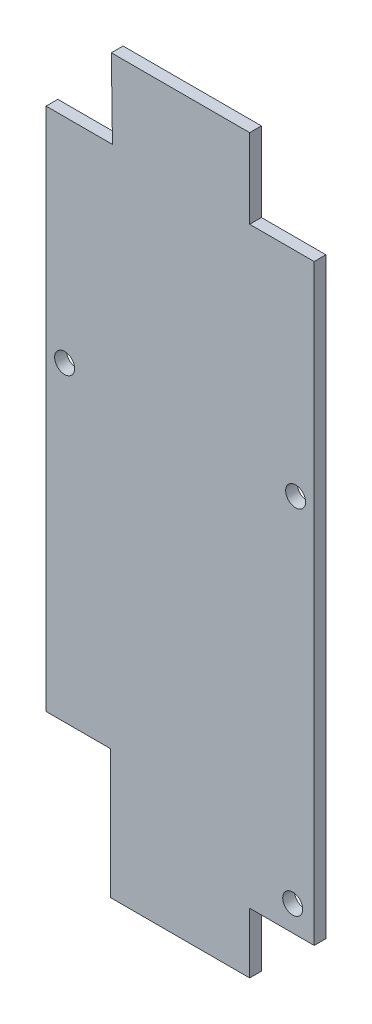
SolidWorks part; units mm, degrees
ref_plane "Front Plane" through (0, 0, 0) normal (0, 0, 1) x (1, 0, 0)
ref_plane "Top Plane" through (0, 0, 0) normal (0, 1, 0) x (1, 0, 0)
ref_plane "Right Plane" through (0, 0, 0) normal (1, 0, 0) x (0, 0, -1)
sketch "Sketch1" plane through (0, 0, 0) normal (0, 0, 1) x (1, 0, 0)
  line L61 (-30.8483, -49.6887) -> (-30.8483, -98.317)
  line L62 (-30.8483, -98.317) -> (-22.1171, -98.317)
  line L63 (-22.1171, -98.317) -> (-22.1171, -115.7795)
  line L64 (-22.1171, -115.7795) -> (-3.283, -115.7795)
  line L65 (-3.283, -115.7795) -> (-3.283, -98.317)
  line L66 (-3.283, -98.317) -> (5.4483, -98.317)
  line L67 (5.4483, -98.317) -> (5.4483, -49.6887)
  line L71 (5.4483, -49.6887) -> (5.4483, -27.4129)
  line L72 (5.4483, -27.4129) -> (-3.283, -27.4129)
  line L73 (-3.283, -27.4129) -> (-3.283, -16.6687)
  line L74 (-3.283, -16.6687) -> (-22.0149, -16.6687)
  line L75 (-22.0149, -16.6687) -> (-21.8622, -27.3367)
  line L76 (-21.8622, -27.3367) -> (-30.8483, -27.3367)
  line L77 (-30.8483, -27.3367) -> (-30.8483, -49.6887)
extrude "Boss-Extrude1" add sketch "Sketch1" along normal blind 1.5875
sketch "Sketch2" plane through (0, 0, 1.5875) normal (0, 0, 1) x (1, 0, 0)
  line L0 (5.4483, -98.317) -> (5.4483, -27.4129) construction
  line L1 (-3.283, -98.317) -> (5.4483, -98.317)
  line L2 (-3.283, -98.317) -> (-3.283, -107.6007)
  line L3 (-3.283, -107.6007) -> (5.4483, -107.6007)
  line L4 (5.4483, -98.317) -> (5.4483, -107.6007)
  line L5 (-3.283, -98.317) -> (5.4483, -107.6007) construction
  line L6 (-3.283, -107.6007) -> (5.4483, -98.317) construction
  line L7 (-3.283, -98.317) -> (5.4483, -98.317) construction
  point P4 (1.0827, -102.9589)
extrude "Boss-Extrude2" add sketch "Sketch2" against normal through all
hole_wizard "#2 Clearance Hole1" positions "Sketch4" profile "Sketch3" hole size "#2" standard "ANSI Inch" end condition through all
sketch "Sketch4" plane through (0, 0, 1.5875) normal (0, 0, 1) x (1, 0, 0)
  point P0 (2.54, -104.14)
  point P2 (-28.3369, -56.1975)
  point P4 (2.9369, -56.1975)
sketch "Sketch3" plane through (2.54, -104.14, 1.5875) normal (1, 0, 0) x (0, -1, 0)
  line L0 (0, 0) -> (0, 1.5875)
  line L1 (0, 1.5875) -> (1.3525, 1.5875)
  line L2 (1.3525, 1.5875) -> (1.3525, 0)
  line L5 (1.3525, 0) -> (0, 0)
  line L11 (0, -6.35) -> (0, 107.95) construction
  dimension "Thru Hole Dia." = 2.7051
  dimension "Thru Hole Depth" = 1.5875
sketch "Sketch5" plane through (0, 0, 0) normal (0, 0, -1) x (-1, 0, 0)
  line L6 (6.7628, -52.8637) -> (6.7628, -57.3087)
  line L7 (18.2563, -52.4827) -> (7.1438, -52.4827)
  line L8 (18.6373, -57.3087) -> (18.6373, -52.8637)
  line L9 (7.1438, -57.6897) -> (18.2563, -57.6897)
  line L10 (6.7628, -52.8637) -> (6.7628, -57.3087)
  line L11 (18.2563, -52.4827) -> (7.1438, -52.4827)
  line L12 (18.6373, -57.3087) -> (18.6373, -52.8637)
  line L13 (7.1438, -57.6897) -> (18.2563, -57.6897)
  line L14 (-1.9685, -42.0687) -> (-1.9685, -46.5137)
  line L15 (9.525, -41.6877) -> (-1.5875, -41.6877)
  line L16 (9.906, -46.5137) -> (9.906, -42.0687)
  line L17 (-1.5875, -46.8947) -> (9.525, -46.8947)
  line L18 (-1.9685, -42.0687) -> (-1.9685, -46.5137)
  line L19 (9.525, -41.6877) -> (-1.5875, -41.6877)
  line L20 (9.906, -46.5137) -> (9.906, -42.0687)
  line L21 (-1.5875, -46.8947) -> (9.525, -46.8947)
  line L22 (15.494, -42.0687) -> (15.494, -46.5137)
  line L23 (26.9875, -41.6877) -> (15.875, -41.6877)
  line L24 (27.3685, -46.5137) -> (27.3685, -42.0687)
  line L25 (15.875, -46.8947) -> (26.9875, -46.8947)
  line L26 (15.494, -42.0687) -> (15.494, -46.5137)
  line L27 (26.9875, -41.6877) -> (15.875, -41.6877)
  line L28 (27.3685, -46.5137) -> (27.3685, -42.0687)
  line L29 (15.875, -46.8947) -> (26.9875, -46.8947)
  line L30 (15.494, -31.2737) -> (15.494, -35.7187)
  line L31 (26.9875, -30.8927) -> (15.875, -30.8927)
  line L32 (27.3685, -35.7187) -> (27.3685, -31.2737)
  line L33 (15.875, -36.0997) -> (26.9875, -36.0997)
  line L34 (15.494, -31.2737) -> (15.494, -35.7187)
  line L35 (26.9875, -30.8927) -> (15.875, -30.8927)
  line L36 (27.3685, -35.7187) -> (27.3685, -31.2737)
  line L37 (15.875, -36.0997) -> (26.9875, -36.0997)
  line L38 (-1.9685, -31.2737) -> (-1.9685, -35.7187)
  line L39 (9.525, -30.8927) -> (-1.5875, -30.8927)
  line L40 (9.906, -35.7187) -> (9.906, -31.2737)
  line L41 (-1.5875, -36.0997) -> (9.525, -36.0997)
  line L42 (-1.9685, -31.2737) -> (-1.9685, -35.7187)
  line L43 (9.525, -30.8927) -> (-1.5875, -30.8927)
  line L44 (9.906, -35.7187) -> (9.906, -31.2737)
  line L45 (-1.5875, -36.0997) -> (9.525, -36.0997)
  line L46 (6.7628, -20.4787) -> (6.7628, -24.9237)
  line L47 (18.2563, -20.0977) -> (7.1438, -20.0977)
  line L48 (18.6373, -24.9237) -> (18.6373, -20.4787)
  line L49 (7.1438, -25.3047) -> (18.2563, -25.3047)
  line L50 (6.7628, -20.4787) -> (6.7628, -24.9237)
  line L51 (18.2563, -20.0977) -> (7.1438, -20.0977)
  line L52 (18.6373, -24.9237) -> (18.6373, -20.4787)
  line L53 (7.1438, -25.3047) -> (18.2563, -25.3047)
  line L54 (9.7473, -71.6915) -> (-1.8097, -71.6915)
  line L55 (9.7473, -77.216) -> (9.7473, -71.6915)
  line L56 (-1.8097, -77.216) -> (9.7473, -77.216)
  line L57 (-1.8097, -71.6915) -> (-1.8097, -77.216)
  line L58 (9.7473, -71.6915) -> (-1.8097, -71.6915)
  line L59 (9.7473, -77.216) -> (9.7473, -71.6915)
  line L60 (-1.8097, -77.216) -> (9.7473, -77.216)
  line L61 (-1.8097, -71.6915) -> (-1.8097, -77.216)
  line L63 (9.7473, -71.1835) -> (9.7473, -65.659)
  line L64 (-1.8097, -71.1835) -> (9.7473, -71.1835)
  line L65 (-1.8097, -65.659) -> (-1.8097, -71.1835)
  line L66 (9.7473, -65.659) -> (-1.8097, -65.659)
  line L67 (9.7473, -71.1835) -> (9.7473, -65.659)
  line L68 (-1.8097, -71.1835) -> (9.7473, -71.1835)
  line L69 (-1.8097, -65.659) -> (-1.8097, -71.1835)
  line L70 (9.7473, -65.659) -> (-1.8097, -65.659)
  line L71 (12.7, -106.6165) -> (12.7, -106.1085) construction
  line L72 (27.2098, -71.1835) -> (27.2098, -65.659)
  line L73 (15.6528, -71.1835) -> (27.2098, -71.1835)
  line L74 (15.6528, -65.659) -> (15.6528, -71.1835)
  line L75 (27.2098, -65.659) -> (15.6528, -65.659)
  line L76 (27.2098, -71.1835) -> (27.2098, -65.659)
  line L77 (15.6528, -71.1835) -> (27.2098, -71.1835)
  line L78 (15.6528, -65.659) -> (15.6528, -71.1835)
  line L79 (27.2098, -65.659) -> (15.6528, -65.659)
  line L80 (27.2098, -71.6915) -> (15.6528, -71.6915)
  line L81 (27.2098, -77.216) -> (27.2098, -71.6915)
  line L82 (15.6528, -77.216) -> (27.2098, -77.216)
  line L83 (15.6528, -71.6915) -> (15.6528, -77.216)
  line L84 (27.2098, -71.6915) -> (15.6528, -71.6915)
  line L85 (27.2098, -77.216) -> (27.2098, -71.6915)
  line L86 (15.6528, -77.216) -> (27.2098, -77.216)
  line L87 (15.6528, -71.6915) -> (15.6528, -77.216)
  line L88 (21.4313, -89.154) -> (21.4313, -88.646) construction
  line L89 (27.2098, -88.646) -> (27.2098, -83.1215)
  line L90 (15.6528, -88.646) -> (27.2098, -88.646)
  line L91 (15.6528, -83.1215) -> (15.6528, -88.646)
  line L92 (27.2098, -83.1215) -> (15.6528, -83.1215)
  line L93 (27.2098, -88.646) -> (27.2098, -83.1215)
  line L94 (15.6528, -88.646) -> (27.2098, -88.646)
  line L95 (15.6528, -83.1215) -> (15.6528, -88.646)
  line L96 (27.2098, -83.1215) -> (15.6528, -83.1215)
  line L97 (3.9688, -89.154) -> (3.9688, -88.646) construction
  line L98 (9.7473, -88.646) -> (9.7473, -83.1215)
  line L99 (-1.8097, -88.646) -> (9.7473, -88.646)
  line L100 (-1.8097, -83.1215) -> (-1.8097, -88.646)
  line L101 (9.7473, -83.1215) -> (-1.8097, -83.1215)
  line L102 (9.7473, -88.646) -> (9.7473, -83.1215)
  line L103 (-1.8097, -88.646) -> (9.7473, -88.646)
  line L104 (-1.8097, -83.1215) -> (-1.8097, -88.646)
  line L105 (9.7473, -83.1215) -> (-1.8097, -83.1215)
  line L106 (27.2098, -89.154) -> (15.6528, -89.154)
  line L107 (27.2098, -94.6785) -> (27.2098, -89.154)
  line L108 (15.6528, -94.6785) -> (27.2098, -94.6785)
  line L109 (15.6528, -89.154) -> (15.6528, -94.6785)
  line L110 (27.2098, -89.154) -> (15.6528, -89.154)
  line L111 (27.2098, -94.6785) -> (27.2098, -89.154)
  line L112 (15.6528, -94.6785) -> (27.2098, -94.6785)
  line L113 (15.6528, -89.154) -> (15.6528, -94.6785)
  line L114 (9.7473, -89.154) -> (-1.8097, -89.154)
  line L115 (9.7473, -94.6785) -> (9.7473, -89.154)
  line L116 (-1.8097, -94.6785) -> (9.7473, -94.6785)
  line L117 (-1.8097, -89.154) -> (-1.8097, -94.6785)
  line L118 (9.7473, -89.154) -> (-1.8097, -89.154)
  line L119 (9.7473, -94.6785) -> (9.7473, -89.154)
  line L120 (-1.8097, -94.6785) -> (9.7473, -94.6785)
  line L121 (-1.8097, -89.154) -> (-1.8097, -94.6785)
  line L122 (3.9688, -71.6915) -> (3.9688, -71.1835) construction
  line L123 (18.4785, -106.1085) -> (18.4785, -100.584)
  line L124 (6.9215, -106.1085) -> (18.4785, -106.1085)
  line L125 (6.9215, -100.584) -> (6.9215, -106.1085)
  line L126 (18.4785, -100.584) -> (6.9215, -100.584)
  line L127 (18.4785, -106.1085) -> (18.4785, -100.584)
  line L128 (6.9215, -106.1085) -> (18.4785, -106.1085)
  line L129 (6.9215, -100.584) -> (6.9215, -106.1085)
  line L130 (18.4785, -100.584) -> (6.9215, -100.584)
  line L131 (18.4785, -106.6165) -> (6.9215, -106.6165)
  line L132 (18.4785, -112.141) -> (18.4785, -106.6165)
  line L133 (6.9215, -112.141) -> (18.4785, -112.141)
  line L134 (6.9215, -106.6165) -> (6.9215, -112.141)
  line L135 (18.4785, -106.6165) -> (6.9215, -106.6165)
  line L136 (18.4785, -112.141) -> (18.4785, -106.6165)
  line L137 (6.9215, -112.141) -> (18.4785, -112.141)
  line L138 (6.9215, -106.6165) -> (6.9215, -112.141)
  line L139 (21.4313, -71.1835) -> (21.4313, -71.6915) construction
  line L147 (-5.4483, -107.6007) -> (3.283, -107.6007)
  line L148 (3.283, -107.6007) -> (3.283, -115.7795)
  line L149 (3.283, -115.7795) -> (22.1171, -115.7795)
  line L150 (22.1171, -115.7795) -> (22.1171, -98.317)
  line L151 (22.1171, -98.317) -> (30.8483, -98.317)
  line L152 (30.8483, -98.317) -> (30.8483, -27.3367)
  line L153 (30.8483, -27.3367) -> (21.8622, -27.3367)
  line L154 (21.8622, -27.3367) -> (22.0149, -16.6687)
  line L155 (22.0149, -16.6687) -> (3.283, -16.6687)
  line L156 (3.283, -16.6687) -> (3.283, -27.4129)
  line L157 (3.283, -27.4129) -> (-5.4483, -27.4129)
  line L158 (-5.4483, -27.4129) -> (-5.4483, -107.6007)
  line L159 (-5.4483, -107.6007) -> (3.283, -107.6007)
  line L160 (3.283, -107.6007) -> (3.283, -115.7795)
  line L161 (3.283, -115.7795) -> (22.1171, -115.7795)
  line L162 (22.1171, -115.7795) -> (22.1171, -98.317)
  line L163 (22.1171, -98.317) -> (30.8483, -98.317)
  line L164 (30.8483, -98.317) -> (30.8483, -27.3367)
  line L165 (30.8483, -27.3367) -> (21.8622, -27.3367)
  line L166 (21.8622, -27.3367) -> (22.0149, -16.6687)
  line L167 (22.0149, -16.6687) -> (3.283, -16.6687)
  line L168 (3.283, -16.6687) -> (3.283, -27.4129)
  line L169 (3.283, -27.4129) -> (-5.4483, -27.4129)
  line L170 (-5.4483, -27.4129) -> (-5.4483, -107.6007)
  circle A0 centre (12.7, -106.3625) radius 2.8509
  circle A1 centre (-2.9369, -56.1975) radius 1.3526
  circle A2 centre (-2.9369, -56.1975) radius 1.3525
  circle A3 centre (28.3369, -56.1975) radius 1.3526
  circle A4 centre (28.3369, -56.1975) radius 1.3526
  circle A5 centre (-2.54, -104.14) radius 1.3526
  circle A6 centre (-2.54, -104.14) radius 1.3525
  circle A7 centre (3.9688, -88.9) radius 2.8509
  circle A8 centre (21.4313, -88.9) radius 2.8509
  circle A9 centre (21.4313, -71.4375) radius 2.8509
  arc A10 (7.1438, -52.4827) -> (6.7628, -52.8637) centre (7.1438, -52.8637) ccw
  arc A11 (18.6373, -52.8637) -> (18.2563, -52.4827) centre (18.2563, -52.8637) ccw
  arc A12 (18.2563, -57.6897) -> (18.6373, -57.3087) centre (18.2563, -57.3087) ccw
  arc A13 (6.7628, -57.3087) -> (7.1438, -57.6897) centre (7.1438, -57.3087) ccw
  arc A14 (7.1438, -52.4827) -> (6.7628, -52.8637) centre (7.1438, -52.8637) ccw
  arc A15 (18.6373, -52.8637) -> (18.2563, -52.4827) centre (18.2563, -52.8637) ccw
  arc A16 (18.2563, -57.6897) -> (18.6373, -57.3087) centre (18.2563, -57.3087) ccw
  arc A17 (6.7628, -57.3087) -> (7.1438, -57.6897) centre (7.1438, -57.3087) ccw
  arc A18 (-1.5875, -41.6877) -> (-1.9685, -42.0687) centre (-1.5875, -42.0687) ccw
  arc A19 (9.906, -42.0687) -> (9.525, -41.6877) centre (9.525, -42.0687) ccw
  arc A20 (9.525, -46.8947) -> (9.906, -46.5137) centre (9.525, -46.5137) ccw
  arc A21 (-1.9685, -46.5137) -> (-1.5875, -46.8947) centre (-1.5875, -46.5137) ccw
  arc A22 (-1.5875, -41.6877) -> (-1.9685, -42.0687) centre (-1.5875, -42.0687) ccw
  arc A23 (9.906, -42.0687) -> (9.525, -41.6877) centre (9.525, -42.0687) ccw
  arc A24 (9.525, -46.8947) -> (9.906, -46.5137) centre (9.525, -46.5137) ccw
  arc A25 (-1.9685, -46.5137) -> (-1.5875, -46.8947) centre (-1.5875, -46.5137) ccw
  arc A26 (15.875, -41.6877) -> (15.494, -42.0687) centre (15.875, -42.0687) ccw
  arc A27 (27.3685, -42.0687) -> (26.9875, -41.6877) centre (26.9875, -42.0687) ccw
  arc A28 (26.9875, -46.8947) -> (27.3685, -46.5137) centre (26.9875, -46.5137) ccw
  arc A29 (15.494, -46.5137) -> (15.875, -46.8947) centre (15.875, -46.5137) ccw
  arc A30 (15.875, -41.6877) -> (15.494, -42.0687) centre (15.875, -42.0687) ccw
  arc A31 (27.3685, -42.0687) -> (26.9875, -41.6877) centre (26.9875, -42.0687) ccw
  arc A32 (26.9875, -46.8947) -> (27.3685, -46.5137) centre (26.9875, -46.5137) ccw
  arc A33 (15.494, -46.5137) -> (15.875, -46.8947) centre (15.875, -46.5137) ccw
  arc A34 (15.875, -30.8927) -> (15.494, -31.2737) centre (15.875, -31.2737) ccw
  arc A35 (27.3685, -31.2737) -> (26.9875, -30.8927) centre (26.9875, -31.2737) ccw
  arc A36 (26.9875, -36.0997) -> (27.3685, -35.7187) centre (26.9875, -35.7187) ccw
  arc A37 (15.494, -35.7187) -> (15.875, -36.0997) centre (15.875, -35.7187) ccw
  arc A38 (15.875, -30.8927) -> (15.494, -31.2737) centre (15.875, -31.2737) ccw
  arc A39 (27.3685, -31.2737) -> (26.9875, -30.8927) centre (26.9875, -31.2737) ccw
  arc A40 (26.9875, -36.0997) -> (27.3685, -35.7187) centre (26.9875, -35.7187) ccw
  arc A41 (15.494, -35.7187) -> (15.875, -36.0997) centre (15.875, -35.7187) ccw
  arc A42 (-1.5875, -30.8927) -> (-1.9685, -31.2737) centre (-1.5875, -31.2737) ccw
  arc A43 (9.906, -31.2737) -> (9.525, -30.8927) centre (9.525, -31.2737) ccw
  arc A44 (9.525, -36.0997) -> (9.906, -35.7187) centre (9.525, -35.7187) ccw
  arc A45 (-1.9685, -35.7187) -> (-1.5875, -36.0997) centre (-1.5875, -35.7187) ccw
  arc A46 (-1.5875, -30.8927) -> (-1.9685, -31.2737) centre (-1.5875, -31.2737) ccw
  arc A47 (9.906, -31.2737) -> (9.525, -30.8927) centre (9.525, -31.2737) ccw
  arc A48 (9.525, -36.0997) -> (9.906, -35.7187) centre (9.525, -35.7187) ccw
  arc A49 (-1.9685, -35.7187) -> (-1.5875, -36.0997) centre (-1.5875, -35.7187) ccw
  arc A50 (7.1438, -20.0977) -> (6.7628, -20.4787) centre (7.1438, -20.4787) ccw
  arc A51 (18.6373, -20.4787) -> (18.2563, -20.0977) centre (18.2563, -20.4787) ccw
  arc A52 (18.2563, -25.3047) -> (18.6373, -24.9237) centre (18.2563, -24.9237) ccw
  arc A53 (6.7628, -24.9237) -> (7.1438, -25.3047) centre (7.1438, -24.9237) ccw
  arc A54 (7.1438, -20.0977) -> (6.7628, -20.4787) centre (7.1438, -20.4787) ccw
  arc A55 (18.6373, -20.4787) -> (18.2563, -20.0977) centre (18.2563, -20.4787) ccw
  arc A56 (18.2563, -25.3047) -> (18.6373, -24.9237) centre (18.2563, -24.9237) ccw
  arc A57 (6.7628, -24.9237) -> (7.1438, -25.3047) centre (7.1438, -24.9237) ccw
  circle A58 centre (3.9688, -71.4375) radius 2.8509
  dimension "D1" = 0
  dimension "D2" = 0
  dimension "D3" = 0
  dimension "D4" = 0
  dimension "D5" = 0
  dimension "D6" = 0
  dimension "D7" = 0
  dimension "D8" = 0
  dimension "D9" = 0
  dimension "D10" = 0
  dimension "D11" = 0
  dimension "D12" = 0
  dimension "D13" = 0
  dimension "D14" = 0
  dimension "D15" = 0
  dimension "D16" = 0
  dimension "D17" = 0
  dimension "D18" = 0
  dimension "D19" = 0
  dimension "D20" = 0
